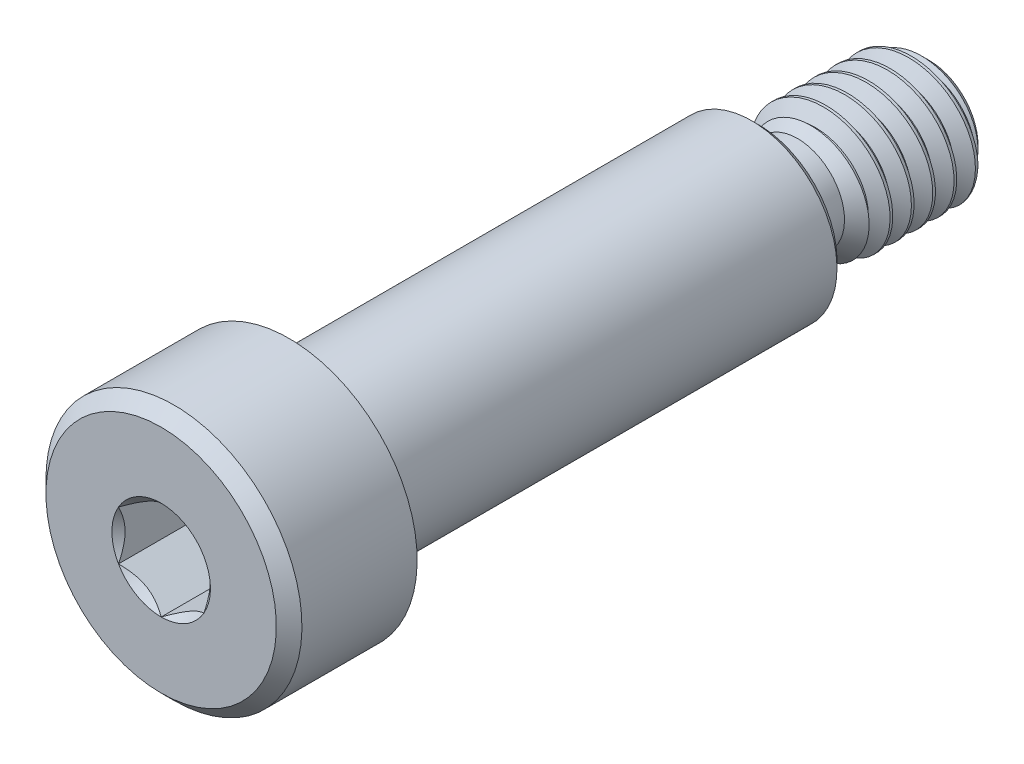
SolidWorks part; units mm, degrees
ref_plane "Front Plane" through (0, 0, 0) normal (0, 0, 1) x (1, 0, 0)
ref_plane "Top Plane" through (0, 0, 0) normal (0, 1, 0) x (1, 0, 0)
ref_plane "Right Plane" through (0, 0, 0) normal (1, 0, 0) x (0, 0, -1)
sketch "Sketch2" plane through (0, 0, 0) normal (1, 0, 0) x (0, 0, -1)
  line L0 (-14.2875, 0) -> (14.2875, 0) construction
  line L1 (-14.2875, 0) -> (-14.2875, 4.7625)
  line L2 (-14.2875, 4.7625) -> (-9.525, 4.7625)
  line L3 (-9.525, 4.7625) -> (-9.525, 3.175)
  line L4 (-9.525, 3.175) -> (7.9375, 3.175)
  line L5 (7.9375, 2.413) -> (14.2875, 2.413)
  line L6 (14.2875, 2.413) -> (14.2875, 0)
  line L7 (14.2379, 2.4989) -> (14.6348, 1.8115) construction
  line L8 (14.6348, 1.8115) -> (15.0316, 2.4989) construction
  line L9 (15.0316, 2.4989) -> (14.2379, 2.4989) construction
  line L10 (14.2875, 2.413) -> (14.982, 2.413) construction
  line L11 (14.6348, 2.4989) -> (14.6348, 2.413) construction
  line L12 (14.6348, 2.413) -> (14.6348, 1.8974) construction
  line L13 (14.6348, 1.8974) -> (14.6348, 1.8115) construction
  line L14 (14.5852, 1.8974) -> (14.6844, 1.8974)
  line L15 (14.2627, 2.456) -> (15.0068, 2.456)
  line L16 (14.6844, 1.8974) -> (15.0068, 2.456)
  line L17 (14.5852, 1.8974) -> (14.2627, 2.456)
  line L18 (14.2875, 0) -> (14.2875, -2.413) construction
  line L19 (7.9375, -3.175) -> (7.9375, 0) construction
  line L20 (7.9375, 0) -> (7.9375, 3.175) construction
  line L21 (-14.2875, 0) -> (-14.2875, -4.7625) construction
  line L22 (9.3885, 1.7494) -> (9.3885, -1.7494) construction
  line L23 (14.2875, 0) -> (9.3885, 0) construction
  point P12 (12.3031, -2.413)
  point P22 (14.6348, 2.456)
  point P23 (6.6675, 0)
  point P25 (-6.6675, 0)
  point P26 (-9.525, -4.7625)
  point P29 (7.9375, -3.175)
  point P40 (9.3885, 0)
  dimension "Head Height" = 4.7625
  dimension "Shoulder Diameter" = 6.35
  dimension "Screw Size Decimal Equivalent" = 4.826
  dimension "Thread Length" = 6.35
  dimension "Head Diameter" = 9.525
  dimension "Pitch" = 0.7937
  dimension "D2" = 0.0992
  dimension "D1" = 1.9844
  dimension "D3" = 7.62
  dimension "D4" = 7.62
  dimension "Shoulder Length" = 17.4625
  dimension "Flat" = 1.451
  dimension "Flat OD" = 3.4988
sketch "Sketch3" plane through (0, 0, 0) normal (0, 0, 1) x (1, 0, 0)
  line L1 (0, 1.8331) -> (-1.5875, 0.9165)
  line L2 (-1.5875, 0.9165) -> (-1.5875, -0.9165)
  line L3 (-1.5875, -0.9165) -> (0, -1.8331)
  line L4 (0, -1.8331) -> (1.5875, -0.9165)
  line L5 (1.5875, -0.9165) -> (1.5875, 0.9165)
  line L6 (1.5875, 0.9165) -> (0, 1.8331)
  circle A0 centre (0, 0) radius 1.5875 construction
  dimension "Drive Size" = 3.175
sketch "Sketch4" plane through (0, 0, 0) normal (1, 0, 0) x (0, 0, -1)
  line L0 (-9.525, 4.7625) -> (-13.8112, 4.7625)
  line L1 (-13.8112, 4.7625) -> (-14.2875, 4.2862)
  line L2 (-9.525, 4.7625) -> (-9.525, 3.175)
  line L7 (-14.2875, 0) -> (14.2875, 0) construction
  line L8 (-9.525, 3.175) -> (7.6835, 3.175)
  line L9 (7.6835, 3.175) -> (7.9375, 2.921)
  line L10 (7.9375, 2.921) -> (7.9375, 0)
  line L11 (7.9375, 3.175) -> (7.9375, 2.921) construction
  line L12 (7.9375, 2.921) -> (7.9375, 2.667) construction
  line L13 (7.9375, 2.667) -> (7.9375, 2.413) construction
  line L14 (-14.2875, 4.2862) -> (-14.2875, 0)
  line L16 (-14.2875, 0) -> (7.9375, 0)
  line L18 (-14.2875, 4.7625) -> (-9.525, 4.7625) construction
  dimension "D3" = 45
  dimension "D5" = 8.5725
  dimension "D1" = 45
revolve "Revolve1" add sketch "Sketch4" angle 360 about L16
sketch "Sketch5" plane through (0, 0, 14.2875) normal (0, 0, 1) x (1, 0, 0)
  line L0 (1.5875, 0.9165) -> (0, 1.8331) construction
  line L1 (1.5875, -0.9165) -> (1.5875, 0.9165) construction
  line L2 (0, -1.8331) -> (1.5875, -0.9165) construction
  line L3 (-1.5875, -0.9165) -> (0, -1.8331) construction
  line L4 (-1.5875, 0.9165) -> (-1.5875, -0.9165) construction
  line L5 (0, 1.8331) -> (-1.5875, 0.9165) construction
  line L6 (1.5875, 0.9165) -> (0, 1.8331)
  line L7 (1.5875, -0.9165) -> (1.5875, 0.9165)
  line L8 (0, -1.8331) -> (1.5875, -0.9165)
  line L9 (-1.5875, -0.9165) -> (0, -1.8331)
  line L10 (-1.5875, 0.9165) -> (-1.5875, -0.9165)
  line L11 (0, 1.8331) -> (-1.5875, 0.9165)
extrude "Cut-Extrude1" cut sketch "Sketch5" against normal blind 3.5719
sketch "Sketch6" plane through (0, 0, 14.2875) normal (0, 0, 1) x (1, 0, 0)
  circle A0 centre (0, 0) radius 1.8331
extrude "Cut-Extrude4" cut sketch "Sketch6" against normal blind 3.5719 draft 45
sketch "Sketch7" plane through (0, 0, 0) normal (1, 0, 0) x (0, 0, -1)
  line L0 (7.9375, 2.413) -> (13.6922, 2.413)
  line L1 (7.9375, 2.413) -> (14.2875, 2.413) construction
  line L2 (13.6922, 2.413) -> (14.2875, 1.8177)
  line L3 (14.2875, 2.413) -> (14.2875, 0) construction
  line L4 (14.2875, 1.8177) -> (14.2875, 0)
  line L5 (14.2875, 0) -> (7.9375, 0)
  line L6 (7.9375, -2.921) -> (7.9375, 2.921) construction
  line L7 (7.9375, 0) -> (7.9375, 2.413)
  dimension "D1" = 45
  dimension "D2" = 0.5953
revolve "Revolve2" add sketch "Sketch7" angle 360 about L5
sketch "Sketch10" plane through (0, 0, 0) normal (1, 0, 0) x (0, 0, -1)
  line L0 (8.6011, 1.7494) -> (9.3885, 1.7494)
  line L1 (9.3885, 1.7494) -> (10.8141, 3.175)
  line L2 (10.8141, 3.175) -> (7.9375, 3.175)
  line L3 (7.9375, 3.175) -> (7.9375, 2.413)
  line L4 (7.9375, -2.921) -> (7.9375, 2.921) construction
  line L5 (14.2875, 0) -> (7.9375, 0) construction
  line L6 (-14.2875, 0) -> (14.2875, 0) construction
  line L7 (-9.525, 3.175) -> (7.9375, 3.175) construction
  line L12 (-9.525, 3.175) -> (-8.89, 3.175)
  line L13 (-9.525, 3.175) -> (-9.525, 2.8575)
  line L14 (-9.525, 2.8575) -> (-9.2075, 2.8575)
  line L15 (-8.89, 3.175) -> (-9.2075, 2.8575)
  arc A0 (7.9375, 2.413) -> (8.6011, 1.7494) centre (8.6011, 2.413) ccw
  dimension "D3" = 45
  dimension "D4" = 45
  dimension "D5" = 5.715
revolve "Cut-Revolve1" cut sketch "Sketch10" angle 360 about L5
fillet "Fillet1" radius 0.1588 1 edges at (0, 2.8575, 9.525)
sketch "Sketch15" plane through (0, 0, 0) normal (0, 0, 1) x (1, 0, 0)
  circle A0 centre (0, 0) radius 4.7625 construction
sketch "Sketch8" plane through (0, 0, -14.2875) normal (0, 0, -1) x (-1, 0, 0)
  circle A1 centre (0, 0) radius 2.413
curve "Helix/Spiral1" pitch 0.7937 height 5.6928 radius 2.413 centre (0, 0, -14.2875) axis (0, 0, 1) start towards (1, 0, 0)
sketch "Sketch9" plane through (0, 0, 0) normal (1, 0, 0) x (0, 0, -1)
  line L0 (14.5852, 1.8974) -> (14.6844, 1.8974) construction
  line L1 (14.6844, 1.8974) -> (15.0068, 2.456) construction
  line L2 (14.2627, 2.456) -> (15.0068, 2.456) construction
  line L3 (14.5852, 1.8974) -> (14.2627, 2.456) construction
  line L4 (14.5852, 1.8974) -> (14.6844, 1.8974)
  line L5 (14.6844, 1.8974) -> (15.0068, 2.456)
  line L6 (14.2627, 2.456) -> (15.0068, 2.456)
  line L7 (14.5852, 1.8974) -> (14.2627, 2.456)
ref_plane "Plane1" through (0, 0, -9.3885) normal (0, 0, 1) x (1, 0, 0)
split "Split1" trim tools "Plane1" bodies to split 138 resulting bodies 139 140
sweep "Cut-Sweep1" cut profiles "Sketch9" path "Helix/Spiral1" align with end faces yes
sketch "Sketch16" plane through (0, 0, -9.3885) normal (0, 0, -1) x (-1, 0, 0)
  circle A2 centre (0, 0) radius 1.4954
  circle A3 centre (0, 0) radius 1.4954
  dimension "D1" = 0.254
extrude "Boss-Extrude1" add sketch "Sketch16" along normal through all draft 60
equation "\"D2@Sketch2\" = \"Pitch@Sketch2\" / 8"
equation "\"D1@Sketch2\"=\"Pitch@Sketch2\"*2.5"
equation "\"D5@Sketch4\"=\"Head Diameter@Sketch2\"*0.9"
equation "\"D1@Cut-Extrude1\"=\"Head Height@Sketch2\"*0.75"
equation "\"D1@Cut-Extrude4\"=\"D1@Cut-Extrude1\""
equation "\"D2@Sketch7\" = \"Pitch@Sketch2\" * 0.75"
equation "\"D3@Helix/Spiral1\"=\"Thread Length@Sketch2\"-\"Flat@Sketch2\"+\"Pitch@Sketch2\""
equation "\"D4@Helix/Spiral1\"=\"Pitch@Sketch2\""
equation "\"D3@Sketch2\"=\"Thread Length@Sketch2\"*1.2"
equation "\"D4@Sketch2\"=\"D3@Sketch2\""
equation "\"Flat@Sketch2\"=\"Thread Length@Sketch2\"*0.2285"
equation "\"Flat OD@Sketch2\"=\"Screw Size Decimal Equivalent@Sketch2\"*.725"
equation "\"D5@Sketch10\"=\"Shoulder Diameter@Sketch2\"*.9"
equation "\"D1@Fillet1\"=\"Shoulder Diameter@Sketch2\"*.025"
